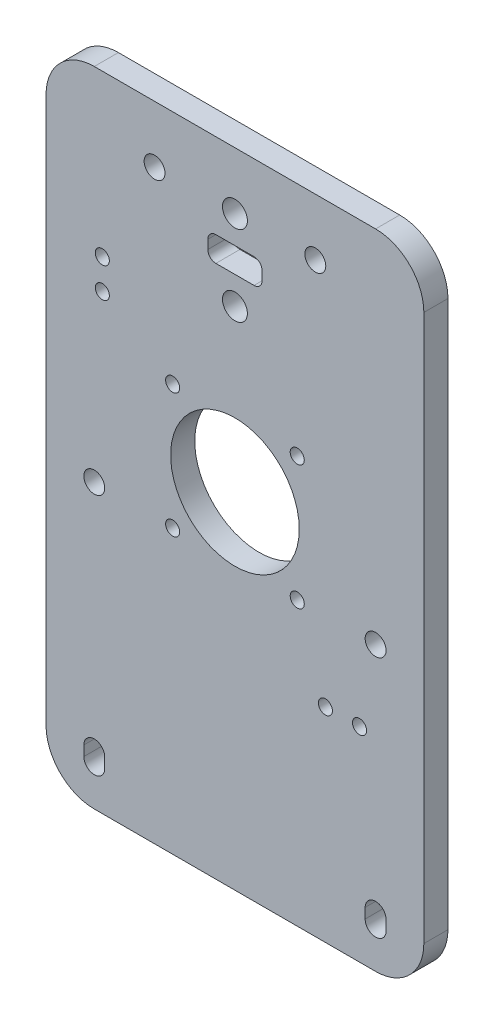
SolidWorks part; units mm, degrees
material "Polycarbonate (PC)"
ref_plane "Спереди" through (0, 0, 0) normal (0, 0, 1) x (1, 0, 0)
ref_plane "Сверху" through (0, 0, 0) normal (0, 1, 0) x (1, 0, 0)
ref_plane "Справа" through (0, 0, 0) normal (1, 0, 0) x (0, 0, -1)
sketch "Model" plane through (0, 0, 0) normal (0, 0, 1) x (1, 0, 0)
  line L0 (-2.3021, 85.8) -> (5.2264, 85.8) construction
  line L1 (6.75, 135.8) -> (-6.75, 135.8) construction
  line L5 (0, 27.6115) -> (0, 0) construction
  line L24 (-35, 64.9169) -> (-35, 77.3985) construction
  line L25 (-31.4983, 12.5) -> (-38.4, 12.5) construction
  line L26 (-31.4983, 10) -> (-38.4, 10) construction
  line L27 (-35, 12.5) -> (-35, 10) construction
  line L28 (-32.4, 12.5) -> (-32.4, 10)
  line L29 (-37.6, 12.5) -> (-37.6, 10)
  line L40 (31.4983, 10) -> (38.4, 10) construction
  line L41 (31.4983, 12.5) -> (38.4, 12.5) construction
  line L42 (35, 64.9169) -> (35, 77.3985) construction
  line L43 (35, 12.5) -> (35, 10) construction
  line L44 (32.4, 12.5) -> (32.4, 10)
  line L45 (37.6, 12.5) -> (37.6, 10)
  line L47 (-26.0102, 145.8) -> (26.0946, 145.8) construction
  line L48 (0, 129.408) -> (0, 90.7064) construction
  line L51 (-38.85, 70.45) -> (-29.8907, 70.45) construction
  line L53 (-16.3166, 125.8) -> (17.7871, 125.8) construction
  line L58 (38.85, 70.45) -> (29.8907, 70.45) construction
  line L4875 (-35, 160) -> (35, 160)
  line L4882 (47, 148) -> (47, 12)
  line L4889 (35, 0) -> (-35, 0)
  line L4896 (-47, 12) -> (-47, 148)
  line L5609 (6.75, 138.9) -> (-6.75, 138.9)
  line L5610 (-6.75, 138.9) -> (-6.75, 132.7)
  line L5611 (-6.75, 132.7) -> (6.75, 132.7)
  line L5612 (6.75, 132.7) -> (6.75, 138.9)
  line L6648 (-6.75, 138.9) -> (6.75, 138.9)
  line L6649 (6.75, 138.9) -> (6.75, 132.7)
  line L6650 (6.75, 132.7) -> (-6.75, 132.7)
  line L6651 (-6.75, 132.7) -> (-6.75, 138.9)
  arc A0 (-47, 12) -> (-35, 0) centre (-35, 12) ccw
  arc A1 (35, 0) -> (47, 12) centre (35, 12) ccw
  arc A2 (47, 148) -> (35, 160) centre (35, 148) ccw
  arc A3 (-35, 160) -> (-47, 148) centre (-35, 148) ccw
  circle A4 centre (0, 85.8) radius 16
  arc A13 (-32.4, 12.5) -> (-37.6, 12.5) centre (-35, 12.5) ccw
  arc A14 (-37.6, 10) -> (-32.4, 10) centre (-35, 10) ccw
  arc A19 (32.4, 12.5) -> (37.6, 12.5) centre (35, 12.5) cw
  arc A20 (37.6, 10) -> (32.4, 10) centre (35, 10) cw
  circle A29 centre (0, 145.8) radius 3.1
  circle A30 centre (-20, 145.8) radius 2.6
  circle A31 centre (20, 145.8) radius 2.6
  circle A32 centre (-35, 70.45) radius 2.6
  circle A33 centre (0, 125.8) radius 3.1
  circle A36 centre (35, 70.45) radius 2.6
  point P17 (0, 0)
  point P77 (-35, 11.25)
  point P114 (35, 11.25)
  point P127 (0, 160)
  dimension "D5" = 32
  dimension "D8" = 94
  dimension "D30" = 5.2
  dimension "D33" = 5.2
  dimension "D35" = 6.2
  dimension "D14" = 12
  dimension "D3" = 160
  dimension "D6" = 60.45
  dimension "D7" = 74.2
  dimension "D9" = 70
  dimension "D10" = 24.2
  dimension "D12" = 20
  dimension "D13" = 20
  dimension "D16" = 2.5
  dimension "D17" = 10
  dimension "D18" = 5.2
  dimension "D25" = 14.2
  dimension "D34" = 20
  dimension "D41" = 13.5
  dimension "D42" = 6.2
extrude "Base" add sketch "Model" along normal blind 6 contours L4875 A3 L4896 A0 L4889 A1 L4882 A2 L45 A20 L44 A19 region at (0, 158.1443, 0)
fillet "FilletCableSlot" radius 2 4 edges at (6.75, 138.9, 3) (-6.75, 138.9, 3) (-6.75, 132.7, 3) (6.75, 132.7, 3)
hole_wizard "Ø3.2 (3.2) Stepper mount Holes" positions "Sketch6" profile "Sketch7" hole size "Ø3.5" standard "ANSI Metric" end condition through all
sketch "Sketch6" plane through (0, 0, 6) normal (0, 0, 1) x (1, 0, 0)
  line L2 (0, 0) -> (0, 95.4376) construction
  line L3 (35, 0) -> (-35, 0) construction
  point P0 (-15.5, 101.3)
  point P3 (-15.5, 70.3)
  point P6 (15.5, 70.3)
  point P9 (15.5, 101.3)
  dimension "D1" = 31
  dimension "D2" = 31
  dimension "D3" = 70.3
sketch "Sketch7" plane through (-15.5, 101.3, 6) normal (1, 0, 0) x (0, -1, 0)
  line L0 (0, 0) -> (0, 6)
  line L1 (0, 6) -> (1.75, 6)
  line L2 (1.75, 6) -> (1.75, 0)
  line L5 (1.75, 0) -> (0, 0)
  line L11 (0, -6.35) -> (0, 107.95) construction
  dimension "Thru Hole Dia." = 3.5
  dimension "Thru Hole Depth" = 6
hole_wizard "Ø3.5 (3.5) SensorMount" positions "Sketch8" profile "Sketch9" hole size "Ø3.5" standard "ANSI Metric" end condition through all
sketch "Sketch8" plane through (0, 0, 6) normal (0, 0, 1) x (1, 0, 0)
  line L0 (-35, 160) -> (35, 160) construction
  line L1 (-47, 12) -> (-47, 148) construction
  point P0 (-33, 120)
  point P2 (-33, 112.5)
  dimension "D1" = 7.5
  dimension "D2" = 40
  dimension "D3" = 14
sketch "Sketch9" plane through (-33, 120, 6) normal (1, 0, 0) x (0, -1, 0)
  line L0 (0, 0) -> (0, 6)
  line L1 (0, 6) -> (1.75, 6)
  line L2 (1.75, 6) -> (1.75, 0)
  line L5 (1.75, 0) -> (0, 0)
  line L11 (0, -6.35) -> (0, 107.95) construction
  dimension "Thru Hole Dia." = 3.5
  dimension "Thru Hole Depth" = 6
hole_wizard "Ø3.5 (3.5) CableMount" positions "Sketch10" profile "Sketch11" hole size "Ø3.5" standard "ANSI Metric" end condition through all
sketch "Sketch10" plane through (0, 0, 6) normal (0, 0, 1) x (1, 0, 0)
  line L0 (35, 0) -> (-35, 0) construction
  line L1 (47, 148) -> (47, 12) construction
  point P0 (22.5, 50.76)
  point P2 (31, 50.76)
  dimension "D1" = 8.5
  dimension "D2" = 50.76
  dimension "D3" = 16
sketch "Sketch11" plane through (22.5, 50.76, 6) normal (1, 0, 0) x (0, -1, 0)
  line L0 (0, 0) -> (0, 6)
  line L1 (0, 6) -> (1.75, 6)
  line L2 (1.75, 6) -> (1.75, 0)
  line L5 (1.75, 0) -> (0, 0)
  line L11 (0, -6.35) -> (0, 107.95) construction
  dimension "Thru Hole Dia." = 3.5
  dimension "Thru Hole Depth" = 6
